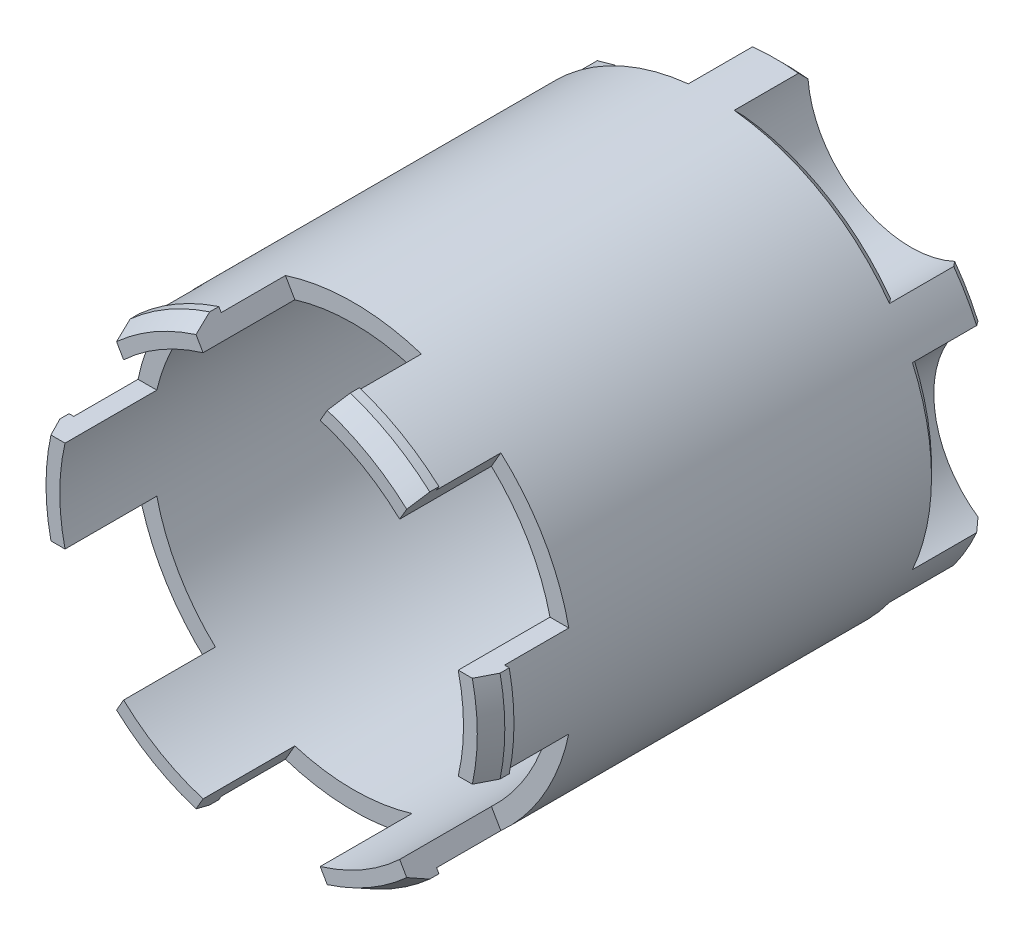
SolidWorks part; units mm, degrees
ref_plane "Front Plane" through (0, 0, 0) normal (0, 0, 1) x (1, 0, 0)
ref_plane "Top Plane" through (0, 0, 0) normal (0, 1, 0) x (1, 0, 0)
ref_plane "Right Plane" through (0, 0, 0) normal (1, 0, 0) x (0, 0, -1)
sketch "Sketch1" plane through (0, 0, 0) normal (0, 0, 1) x (1, 0, 0)
  line L0 (-1.4524, 0) -> (71.008, 0) construction
  line L1 (0, 0) -> (0, 72.303) construction
  line L2 (21.4243, 5) -> (23.9844, 5)
  line L3 (21.4243, -5) -> (23.9844, -5)
  line L4 (15.0423, -16.054) -> (16.3223, -18.2711)
  line L5 (6.382, -21.054) -> (7.6621, -23.2711)
  line L6 (-6.382, -21.054) -> (-7.6621, -23.2711)
  line L7 (-15.0423, -16.054) -> (-16.3223, -18.2711)
  line L8 (-21.4243, -5) -> (-23.9844, -5)
  line L9 (-21.4243, 5) -> (-23.9844, 5)
  line L10 (-15.0423, 16.054) -> (-16.3223, 18.2711)
  line L11 (-6.382, 21.054) -> (-7.6621, 23.2711)
  line L12 (6.382, 21.054) -> (7.6621, 23.2711)
  line L13 (15.0423, 16.054) -> (16.3223, 18.2711)
  circle A1 centre (0, 0) radius 24
  circle A2 centre (0, 0) radius 22
  arc A3 (21.9216, 9.7695) -> (21.9216, -9.7695) centre (27.5, 0) ccw
  arc A4 (19.358, 10.4532) -> (19.358, -10.4532) centre (27.5, 0) ccw
  circle A5 centre (27.5, 0) radius 13.25 construction
  circle A6 centre (27.5, 0) radius 11.25 construction
  arc A7 (18.7317, -11.5379) -> (0.6262, -21.9911) centre (13.75, -23.8157) ccw
  arc A8 (19.4215, -14.0999) -> (2.5001, -23.8694) centre (13.75, -23.8157) ccw
  arc A9 (-0.6262, -21.9911) -> (-18.7317, -11.5379) centre (-13.75, -23.8157) ccw
  arc A10 (-2.5001, -23.8694) -> (-19.4215, -14.0999) centre (-13.75, -23.8157) ccw
  arc A11 (-19.358, -10.4532) -> (-19.358, 10.4532) centre (-27.5, 0) ccw
  arc A12 (-21.9216, -9.7695) -> (-21.9216, 9.7695) centre (-27.5, 0) ccw
  arc A13 (-18.7317, 11.5379) -> (-0.6262, 21.9911) centre (-13.75, 23.8157) ccw
  arc A14 (-19.4215, 14.0999) -> (-2.5001, 23.8694) centre (-13.75, 23.8157) ccw
  arc A15 (0.6262, 21.9911) -> (18.7317, 11.5379) centre (13.75, 23.8157) ccw
  arc A16 (2.5001, 23.8694) -> (19.4215, 14.0999) centre (13.75, 23.8157) ccw
  arc A17 (16.724, 17.2136) -> (6.5455, 23.0902) centre (0, 0) ccw construction
  circle A18 centre (0, 0) radius 24.5
  point P50 (0, 0)
  point P76 (0, 0)
  dimension "D2" = 22.5
  dimension "D6" = 0
  dimension "D1" = 2
  dimension "D7" = 0.5
  dimension "D3" = 27.5
  dimension "D8" = 10
  dimension "D4" = 2
  dimension "D5" = 6
  dimension "D9" = 6
extrude "Boss-Extrude1" add sketch "Sketch1" along normal blind 3 and the other way blind 37 contours A1 A3 A2 L2 | A2 L3 A1 L2 | A2 A3 A1 L3 | A8 A1 A3 A2 | A1 A8 A2 L4 | A2 L5 A1 L4 | A2 A8 A1 L5 | A10 A1 A8 A2 | A1 A10 A2 L6 | A2 L7 A1 L6 | A2 A10 A1 L7 | A12 A1 A10 A2 | A1 A12 A2 L8 | A2 L9 A1 L8 | A2 A12 A1 L9 | A14 A1 A12 A2 | A1 A14 A2 L10 | A2 L11 A1 L10 | A2 A14 A1 L11 | A16 A1 A14 A2 | A1 A16 A2 L12 | A2 L13 A1 L12 | A2 A16 A1 L13 | A16 A2 A3 A1 region at (21.8731, 7.1433, 0) region at (22.816, 0, 0) region at (19.8673, 11.4704, 0) region at (21.8731, -7.1433, 0) region at (19.8673, -11.4704, 0) region at (17.1228, 15.371, 0) region at (11.408, 19.7592, 0) region at (0, 22.9408, 0) region at (17.1228, -15.371, 0) region at (4.7503, 22.5143, 0) region at (0, -22.9408, 0) region at (11.408, -19.7592, 0) region at (-4.7503, 22.5143, 0) region at (-11.408, 19.7592, 0) region at (-19.8673, 11.4704, 0) region at (4.7503, -22.5143, 0) region at (-17.1228, 15.371, 0) region at (-4.7503, -22.5143, 0) region at (-19.8673, -11.4704, 0) region at (-11.408, -19.7592, 0) region at (-21.8731, 7.1433, 0) region at (-22.816, 0, 0) region at (-17.1228, -15.371, 0) region at (-21.8731, -7.1433, 0)
extrude "Boss-Extrude2" add sketch "Sketch1<5>" along normal blind 2 from surface contours A16 A2 A3 A1 | A8 A1 A3 A2 | A10 A1 A8 A2 | A12 A1 A10 A2 | A14 A1 A12 A2 | A16 A1 A14 A2 | A2 region at (19.8673, 11.4704, 0) region at (19.8673, -11.4704, 0) region at (0, 22.9408, 0) region at (0, -22.9408, 0) region at (-19.8673, 11.4704, 0) region at (-19.8673, -11.4704, 0) starting at face at (24, 0, -37)
sketch "Sketch1<5>" plane through (0, 0, 0) normal (0, 0, 1) x (1, 0, 0) same geometry as "Sketch1"
extrude "Boss-Extrude4" add sketch "Sketch1<7>" against normal blind 5 from surface contours A14 A2 A13 | A14 A1 A12 A2 | A12 A2 A11 | A12 A1 A10 A2 | A10 A2 A9 | A10 A1 A8 A2 | A8 A2 A7 | A8 A1 A3 A2 | A2 A4 A3 | A16 A2 A3 A1 | A16 A2 A15 | A16 A1 A14 A2 region at (16.0325, 0, 0) region at (19.8673, 11.4704, 0) region at (19.8673, -11.4704, 0) region at (7.232, 12.5263, 0) region at (0, 22.9408, 0) region at (17.9956, -12.2795, 0) region at (-7.232, 12.5263, 0) region at (0, -22.9408, 0) region at (-19.8673, 11.4704, 0) region at (-1.6366, -21.7244, 0) region at (-14.4675, 0, 0) region at (-19.8673, -11.4704, 0) starting at face at (24, 0, -37)
sketch "Sketch1<7>" plane through (0, 0, 0) normal (0, 0, 1) x (1, 0, 0) same geometry as "Sketch1"
extrude "Boss-Extrude5" add sketch "Sketch1<8>" against normal blind 2 from surface contours A14 A2 A13 | A16 A1 A14 A2 | A16 A2 A15 | A15 A2 A13 A11 A9 A7 A4 | A2 A4 A3 | A16 A2 A3 A1 | A8 A1 A3 A2 | A8 A2 A7 | A10 A1 A8 A2 | A10 A2 A9 | A12 A1 A10 A2 | A12 A2 A11 | A14 A1 A12 A2 region at (16.0325, 0, 0) region at (19.8673, 11.4704, 0) region at (0, 0, 0) region at (19.8673, -11.4704, 0) region at (7.232, 12.5263, 0) region at (0, 22.9408, 0) region at (17.9956, -12.2795, 0) region at (-7.232, 12.5263, 0) region at (0, -22.9408, 0) region at (-19.8673, 11.4704, 0) region at (-1.6366, -21.7244, 0) region at (-14.4675, 0, 0) region at (-19.8673, -11.4704, 0) starting at face at (0, 0, -42)
sketch "Sketch1<8>" plane through (0, 0, 0) normal (0, 0, 1) x (1, 0, 0) same geometry as "Sketch1"
chamfer "Chamfer1" distance 1 angle 45 12 edges at (-20.7846, 12, -44) (-20.7846, -12, -44) (0, -24, -44) (20.7846, -12, -44) (20.7846, 12, -44) (0, 24, -44) (24, 0, -37) (12, -20.7846, -37) (-12, -20.7846, -37) (-24, 0, -37) (-12, 20.7846, -37) (12, 20.7846, -37)
extrude "Boss-Extrude6" add sketch "Sketch1<9>" along normal blind 10 from surface contours A2 L3 A1 L2 | A2 L13 A1 L12 | A2 L11 A1 L10 | A2 L9 A1 L8 | A2 L7 A1 L6 | A2 L5 A1 L4 region at (22.816, 0, 0) region at (11.408, 19.7592, 0) region at (11.408, -19.7592, 0) region at (-11.408, 19.7592, 0) region at (-11.408, -19.7592, 0) region at (-22.816, 0, 0) starting at face at (24, 0, 3)
sketch "Sketch1<9>" plane through (0, 0, 0) normal (0, 0, 1) x (1, 0, 0) same geometry as "Sketch1"
extrude "Boss-Extrude7" add sketch "Sketch1<10>" against normal blind 3 from surface contours L3 A18 L2 A1 | L13 A18 L12 A1 | L11 A18 L10 A1 | L9 A18 L8 A1 | L7 A18 L6 A1 | L5 A18 L4 A1 region at (24.076, 0, 0) region at (12.038, 20.8505, 0) region at (12.038, -20.8505, 0) region at (-12.038, 20.8505, 0) region at (-12.038, -20.8505, 0) region at (-24.076, 0, 0) starting at face at (22.7244, 0, 13)
sketch "Sketch1<10>" plane through (0, 0, 0) normal (0, 0, 1) x (1, 0, 0) same geometry as "Sketch1"
chamfer "Chamfer2" distance 2 distance2 1 6 edges at (-12.25, 21.2176, 13) (-24.5, 0, 13) (-12.25, -21.2176, 13) (12.25, -21.2176, 13) (24.5, 0, 13) (12.25, 21.2176, 13) first distance on face at (-12.1211, 20.9943, 11.5) first distance on face at (-24.2422, 0, 11.5) first distance on face at (-12.1211, -20.9943, 11.5) first distance on face at (12.1211, -20.9943, 11.5) first distance on face at (24.2422, 0, 11.5) first distance on face at (12.1211, 20.9943, 11.5)
